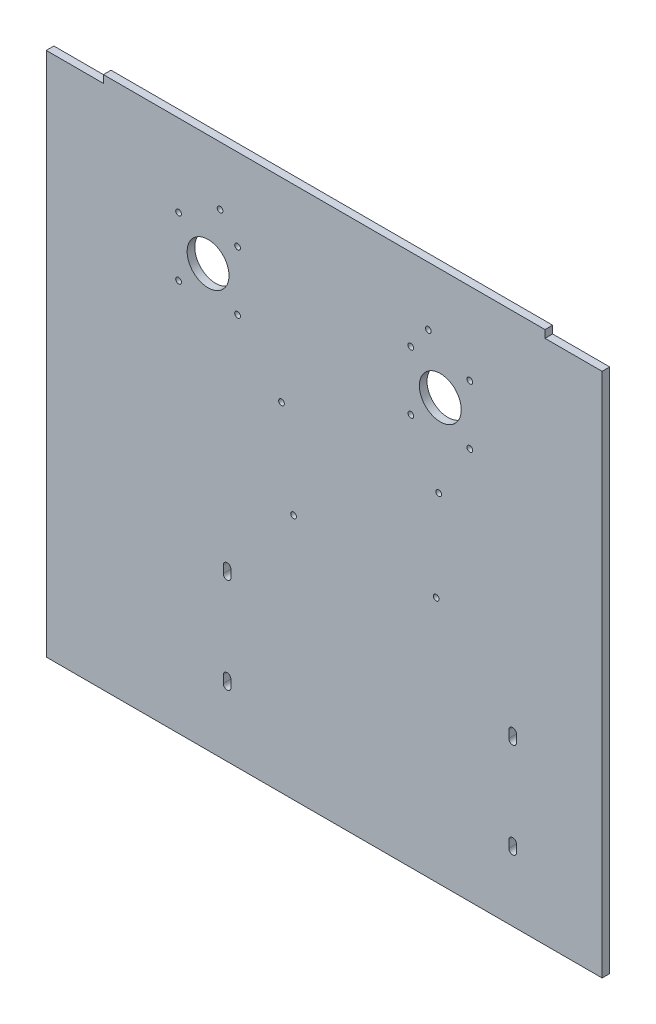
SolidWorks part; units mm, degrees
ref_plane "Front Plane" through (0, 0, 0) normal (0, 0, 1) x (1, 0, 0)
ref_plane "Top Plane" through (0, 0, 0) normal (0, 1, 0) x (1, 0, 0)
ref_plane "Right Plane" through (0, 0, 0) normal (1, 0, 0) x (0, 0, -1)
sketch "Sketch1" plane through (0, 0, 0) normal (0, 0, 1) x (1, 0, 0)
  line L0 (-45.5, 82.5) -> (-76.5, 82.5) construction
  line L1 (146, -123.5) -> (-146, -123.5)
  line L2 (146, -123.5) -> (146, 123.5)
  line L3 (146, 123.5) -> (-146, 123.5)
  line L4 (-146, -123.5) -> (-146, 123.5)
  line L5 (146, -123.5) -> (-146, 123.5) construction
  line L6 (146, 123.5) -> (-146, -123.5) construction
  line L7 (-45.5, 82.5) -> (-45.5, 113.5) construction
  line L8 (-45.5, 113.5) -> (-76.5, 113.5) construction
  line L9 (-76.5, 82.5) -> (-76.5, 113.5) construction
  line L10 (-45.5, 82.5) -> (-76.5, 113.5) construction
  line L11 (-45.5, 113.5) -> (-76.5, 82.5) construction
  line L12 (0, 123.5) -> (0, -133.2191) construction
  line L13 (45.5, 113.5) -> (76.5, 82.5) construction
  line L14 (45.5, 82.5) -> (76.5, 113.5) construction
  line L15 (76.5, 82.5) -> (76.5, 113.5) construction
  line L16 (45.5, 113.5) -> (76.5, 113.5) construction
  line L17 (45.5, 82.5) -> (45.5, 113.5) construction
  line L18 (45.5, 82.5) -> (76.5, 82.5) construction
  line L19 (-175.5662, 125.75) -> (218.0802, 125.75) construction
  line L20 (-146, 123.5) -> (146, 123.5)
  line L21 (-146, 123.5) -> (-146, 156.5)
  line L22 (-146, 156.5) -> (146, 156.5)
  line L23 (146, 123.5) -> (146, 156.5)
  line L24 (0, 156.5) -> (0, 123.5) construction
  line L25 (-146, 140) -> (146, 140) construction
  line L26 (146, 154.5) -> (116, 154.5) construction
  line L27 (-146, 156.5) -> (-116, 156.5)
  line L28 (-146, 156.5) -> (-146, 152.5)
  line L29 (-146, 152.5) -> (-116, 152.5)
  line L30 (-116, 156.5) -> (-116, 152.5)
  line L31 (-131, 152.5) -> (-131, 156.5) construction
  line L32 (-146, 154.5) -> (-116, 154.5) construction
  line L33 (131, 152.5) -> (131, 156.5) construction
  line L34 (116, 156.5) -> (116, 152.5)
  line L35 (146, 152.5) -> (116, 152.5)
  line L36 (146, 156.5) -> (146, 152.5)
  line L37 (146, 156.5) -> (116, 156.5)
  line L38 (-51, -39) -> (-51, -35.0783) construction
  line L39 (-53, -39) -> (-53, -35.0783)
  line L40 (-49, -39) -> (-49, -35.0783)
  line L41 (-51, -89) -> (-51, -85.0783) construction
  line L42 (-53, -89) -> (-53, -85.0783)
  line L43 (-49, -89) -> (-49, -85.0783)
  line L44 (99, -39) -> (99, -35.0783) construction
  line L45 (97, -39) -> (97, -35.0783)
  line L46 (101, -39) -> (101, -35.0783)
  line L47 (99, -89) -> (99, -85.0783) construction
  line L48 (97, -89) -> (97, -85.0783)
  line L49 (101, -89) -> (101, -85.0783)
  circle A0 centre (-76.5, 113.5) radius 1.5
  circle A1 centre (-45.5, 113.5) radius 1.5
  circle A2 centre (76.5, 82.5) radius 1.5
  circle A3 centre (-61, 98) radius 11
  circle A4 centre (-45.5, 82.5) radius 1.5
  circle A5 centre (-76.5, 82.5) radius 1.5
  circle A6 centre (45.5, 82.5) radius 1.5
  circle A7 centre (61, 98) radius 11
  circle A8 centre (45.5, 113.5) radius 1.5
  circle A9 centre (76.5, 113.5) radius 1.5
  circle A10 centre (99, -39) radius 2 construction
  circle A11 centre (99, -89) radius 2 construction
  circle A12 centre (-51, -39) radius 2 construction
  circle A13 centre (-51, -89) radius 2 construction
  circle A14 centre (60.1213, 54.1951) radius 1.5
  circle A15 centre (-54.7, 125.75) radius 1.5
  circle A16 centre (-16.0787, 5.9351) radius 1.5
  circle A17 centre (58.8513, 5.9351) radius 1.5
  circle A18 centre (-22.4287, 54.1951) radius 1.5
  circle A19 centre (54.7, 125.75) radius 1.5
  arc A20 (-53, -39) -> (-49, -39) centre (-51, -39) ccw
  arc A21 (-49, -35.0783) -> (-53, -35.0783) centre (-51, -35.0783) ccw
  arc A22 (97, -39) -> (101, -39) centre (99, -39) ccw
  arc A23 (-53, -89) -> (-49, -89) centre (-51, -89) ccw
  arc A24 (-49, -85.0783) -> (-53, -85.0783) centre (-51, -85.0783) ccw
  arc A25 (101, -35.0783) -> (97, -35.0783) centre (99, -35.0783) ccw
  arc A26 (97, -89) -> (101, -89) centre (99, -89) ccw
  arc A27 (101, -85.0783) -> (97, -85.0783) centre (99, -85.0783) ccw
  point P0 (0, 0)
  point P63 (131, 154.5)
  point P65 (-51, -37.0392)
  point P73 (-51, -87.0392)
  point P79 (99, -37.0392)
  point P86 (99, -87.0392)
  point P132 (-131, 154.5)
  point P274 (0, 140)
  dimension "D3" = 22
  dimension "D5" = 3
  dimension "D6" = 85
  dimension "D8" = 3
  dimension "D9" = 3
  dimension "D10" = 3
  dimension "D11" = 2
  dimension "D12" = 2
  dimension "D13" = 2
  dimension "D14" = 2
  dimension "D19" = 3
  dimension "D20" = 3
  dimension "D21" = 3
  dimension "D22" = 3
  dimension "D31" = 3
  dimension "D35" = 2
  dimension "D1" = 292
  dimension "D2" = 247
  dimension "D4" = 31
  dimension "D7" = 10
  dimension "D15" = 95
  dimension "D16" = 150
  dimension "D17" = 50
  dimension "D18" = 34.5
  dimension "D23" = 82.55
  dimension "D24" = 48.26
  dimension "D25" = 74.93
  dimension "D26" = 48.26
  dimension "D27" = 69.3049
  dimension "D28" = 85.8787
  dimension "D29" = 33
  dimension "D30" = 2.25
  dimension "D32" = 54.7
  dimension "D33" = 30
  dimension "D34" = 4
extrude "Boss-Extrude1" add sketch "Sketch1" along normal blind 4 contours L4 L1 L2 L3 A18 A17 A16 A14 A13 A12 A11 A10 A8 A6 A5 A4 A3 A0 A1 A2 A7 A9 | L3 L23 L22 L21 region at (-0.0461, -1.0382, 0) region at (0, 139.6505, 0)
